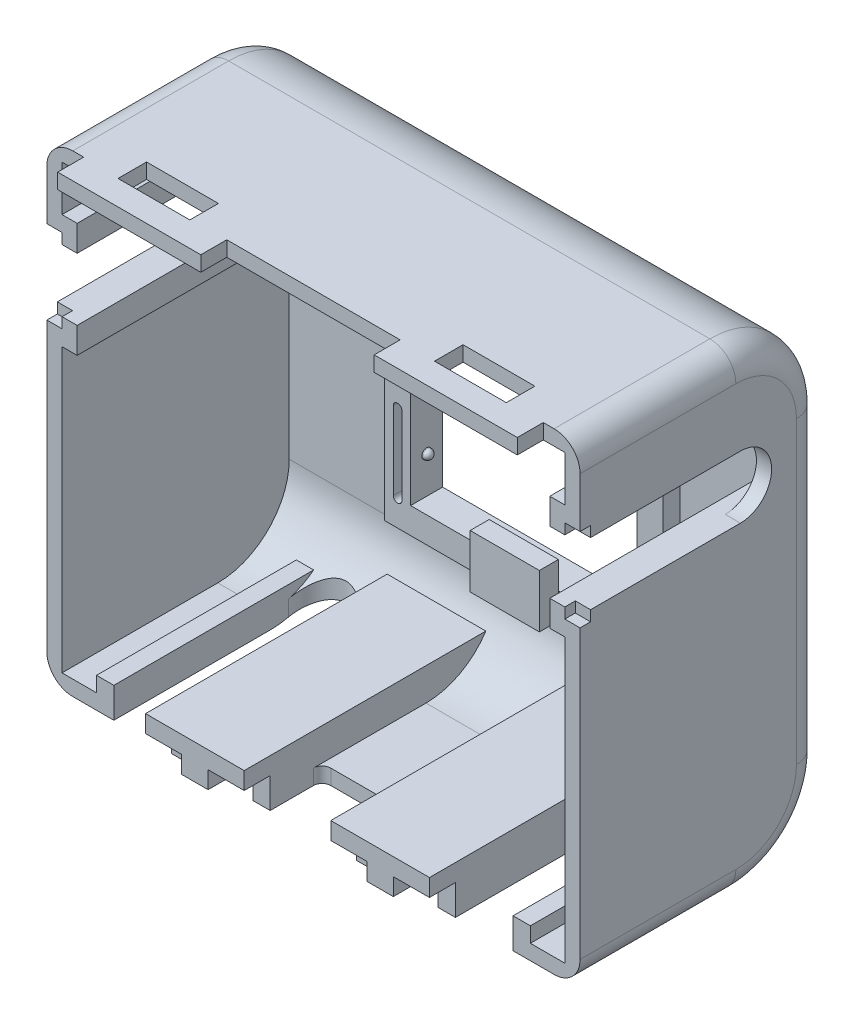
SolidWorks part; units mm, degrees
ref_plane "正面" through (0, 0, 0) normal (0, 0, 1) x (1, 0, 0)
ref_plane "平面" through (0, 0, 0) normal (0, 1, 0) x (1, 0, 0)
ref_plane "右側面" through (0, 0, 0) normal (1, 0, 0) x (0, 0, -1)
sketch "ｽｹｯﾁ1" plane through (0, 0, 0) normal (0, 0, 1) x (1, 0, 0)
  line L0 (0, 0) -> (54, 0) construction
  line L1 (0, 20) -> (54, 20) construction
  line L2 (-1.5, 45.5) -> (55.5, 45.5)
  line L3 (54, 0) -> (54, 40) construction
  line L4 (54, 40) -> (0, 40) construction
  line L5 (0, 40) -> (0, 0) construction
  line L6 (55.5, 45.5) -> (55.5, -5.5)
  line L7 (55.5, -5.5) -> (-1.5, -5.5)
  line L8 (-1.5, -5.5) -> (-1.5, 45.5)
  line L9 (27, 45.5) -> (27, -5.5) construction
  circle A0 centre (2, 2) radius 1.1 construction
  circle A1 centre (52, 2) radius 1.1 construction
  circle A2 centre (52, 38) radius 1.1 construction
  circle A3 centre (2, 38) radius 1.1 construction
  circle A4 centre (2, 38) radius 0.9
  circle A5 centre (2, 38) radius 1.8491
  circle A6 centre (2, 2) radius 1.8491
  circle A7 centre (52, 2) radius 1.8491
  circle A8 centre (52, 38) radius 1.8491
  circle A9 centre (52, 38) radius 0.9
  circle A10 centre (52, 2) radius 0.9
  circle A11 centre (2, 2) radius 0.9
  circle A12 centre (11.0176, 28.1) radius 7
  circle A13 centre (42.9824, 28.1) radius 7
  circle A14 centre (16.5, 8.4) radius 7
  circle A15 centre (37.5, 8.4) radius 7
  dimension "D3" = 2.2
  dimension "D8" = 1.8
  dimension "D9" = 14
  dimension "D10" = 14
  dimension "D11" = 14
  dimension "D12" = 14
  dimension "D1" = 40
  dimension "D2" = 54
  dimension "D4" = 25.5
  dimension "D5" = 25.5
  dimension "D6" = 1.5
  dimension "D7" = 1.5
sketch "ｽｹｯﾁ2" plane through (0, 0, 0) normal (1, 0, 0) x (0, 0, -1)
  line L2 (0, 0) -> (18, 0)
  line L3 (0, 0) -> (0, 54.6)
  line L4 (0, 54.6) -> (18, 54.6)
  line L5 (28, 10) -> (28, 44.6)
  arc A0 (18, 0) -> (28, 10) centre (18, 10) ccw
  arc A1 (18, 54.6) -> (28, 44.6) centre (18, 44.6) cw
  point P8 (28, 54.6)
  dimension "D3" = 10
  dimension "D1" = 28
  dimension "D2" = 54.6
extrude "ﾎﾞｽ - 押し出し1" add sketch "ｽｹｯﾁ2" along normal blind 61.6
shell "ｼｪﾙ1" thickness 1.75 removed face at (30.8, 27.3, 0)
fillet "ﾌｨﾚｯﾄ2" radius 3 10 edges at (0, 54.6, -9) (61.6, 54.6, -9) (0, 0, -9) (0, 2.9289, -25.0711) (0, 27.3, -28) (0, 51.6711, -25.0711) (61.6, 0, -9) (61.6, 2.9289, -25.0711) (61.6, 27.3, -28) (61.6, 51.6711, -25.0711)
sketch "ｽｹｯﾁ3" plane through (0, 0, -26.25) normal (0, 0, -1) x (-1, 0, 0)
  line L0 (-30.8, 44.6) -> (-30.8, 10) construction
  line L1 (-58.6, 44.6) -> (-3, 44.6) construction
  line L2 (-58.6, 10) -> (-3, 10) construction
  line L3 (-30.8, 39.325) -> (-30.8, 15.475) construction
  line L4 (-24.3025, 31.1) -> (-24.3025, 39.225) construction
  line L5 (-34.9975, 31.1) -> (-34.9975, 23.7) construction
  line L6 (-26.6025, 31.1) -> (-26.6025, 23.7) construction
  line L7 (-39.5975, 31.1) -> (-34.9975, 31.1) construction
  line L8 (-39.5975, 31.1) -> (-39.5975, 23.7) construction
  line L9 (-39.5975, 23.7) -> (-34.9975, 23.7) construction
  line L10 (-37.2975, 39.225) -> (-37.2975, 15.575) construction
  line L11 (-22.0025, 23.7) -> (-26.6025, 23.7) construction
  line L12 (-22.0025, 31.1) -> (-22.0025, 23.7) construction
  line L13 (-22.0025, 31.1) -> (-26.6025, 31.1) construction
  line L14 (-30.8, 27.3) -> (-58.6, 27.3) construction
  line L15 (-58.6, 44.6) -> (-58.6, 10) construction
  line L20 (-43.88, 40.48) -> (-43.88, 14.32)
  line L21 (-17.72, 14.32) -> (-17.72, 40.48)
  line L22 (-16.22, 40.48) -> (-16.22, 31.48) construction
  line L23 (-15.72, 40.48) -> (-15.72, 31.48)
  line L24 (-16.72, 40.48) -> (-16.72, 31.48)
  line L25 (-17.72, 40.48) -> (-16.22, 40.48) construction
  line L26 (-17.72, 40.48) -> (-43.88, 40.48)
  line L27 (-16.22, 14.32) -> (-16.22, 23.32) construction
  line L28 (-30.8, 40.8494) -> (-30.8, 13.9506) construction
  line L29 (-45.38, 40.48) -> (-45.38, 31.48) construction
  line L30 (-45.88, 40.48) -> (-45.88, 31.48)
  line L31 (-44.88, 40.48) -> (-44.88, 31.48)
  line L32 (-15.72, 14.32) -> (-15.72, 23.32)
  line L33 (-17.72, 14.32) -> (-43.88, 14.32)
  line L34 (-43.88, 27.4) -> (-17.72, 27.4) construction
  line L35 (-16.72, 14.32) -> (-16.72, 23.32)
  line L36 (-45.38, 14.32) -> (-45.38, 23.32) construction
  line L37 (-45.88, 14.32) -> (-45.88, 23.32)
  line L38 (-44.88, 14.32) -> (-44.88, 23.32)
  arc A0 (-15.72, 40.48) -> (-16.72, 40.48) centre (-16.22, 40.48) ccw
  arc A1 (-16.72, 31.48) -> (-15.72, 31.48) centre (-16.22, 31.48) ccw
  arc A2 (-45.88, 40.48) -> (-44.88, 40.48) centre (-45.38, 40.48) cw
  arc A3 (-44.88, 31.48) -> (-45.88, 31.48) centre (-45.38, 31.48) cw
  arc A4 (-15.72, 14.32) -> (-16.72, 14.32) centre (-16.22, 14.32) cw
  arc A5 (-16.72, 23.32) -> (-15.72, 23.32) centre (-16.22, 23.32) cw
  arc A6 (-45.88, 14.32) -> (-44.88, 14.32) centre (-45.38, 14.32) ccw
  arc A7 (-44.88, 23.32) -> (-45.88, 23.32) centre (-45.38, 23.32) ccw
  point P32 (-16.22, 35.98)
  point P43 (-16.22, 18.82)
  point P53 (-45.38, 35.98)
  point P59 (-45.38, 18.82)
  dimension "D4" = 1
  dimension "D5" = 1
  dimension "D6" = 13.08
extrude "ｶｯﾄ - 押し出し1" cut sketch "ｽｹｯﾁ3" along normal up to vertex (1.75 mm away) up to point (3, 10, -28)
sketch "ｽｹｯﾁ4" [suppressed] plane through (0, 0, -34) normal (0, 0, 1) x (1, 0, 0)
  line L6 (22.0025, 31.1) -> (26.6025, 31.1) construction
  line L7 (22.0025, 23.7) -> (22.0025, 31.1) construction
  line L8 (22.0025, 23.7) -> (26.6025, 23.7) construction
  line L9 (26.6025, 31.1) -> (26.6025, 23.7) construction
  line L10 (39.5975, 23.7) -> (34.9975, 23.7) construction
  line L11 (34.9975, 31.1) -> (34.9975, 23.7) construction
  line L12 (17.9225, 15.575) -> (30.6725, 15.575)
  line L13 (30.6725, 15.575) -> (43.6775, 15.575)
  line L14 (43.6775, 15.575) -> (43.6775, 39.225)
  line L15 (43.6775, 39.225) -> (30.6725, 39.225)
  line L16 (30.6725, 39.225) -> (17.9225, 39.225)
  line L17 (17.9225, 39.225) -> (17.9225, 15.575)
  line L18 (39.5975, 31.1) -> (34.9975, 31.1) construction
  line L19 (39.5975, 31.1) -> (39.5975, 23.7) construction
  line L20 (22.0025, 31.1) -> (26.6025, 31.1)
  line L21 (22.0025, 23.7) -> (22.0025, 31.1)
  line L22 (22.0025, 23.7) -> (26.6025, 23.7)
  line L23 (26.6025, 31.1) -> (26.6025, 23.7)
  line L24 (39.5975, 23.7) -> (34.9975, 23.7)
  line L25 (34.9975, 31.1) -> (34.9975, 23.7)
  line L26 (39.5975, 31.1) -> (34.9975, 31.1)
  line L27 (39.5975, 31.1) -> (39.5975, 23.7)
extrude "ﾎﾞｽ - 押し出し2" [suppressed] add sketch "ｽｹｯﾁ4" along normal blind 3.7
sketch "ｽｹｯﾁ5" [suppressed] plane through (0, 0, -30.3) normal (0, 0, 1) x (1, 0, 0)
  line L9 (20.8725, 31.35) -> (20.8725, 23.45)
  line L10 (17.9225, 31.35) -> (17.9225, 23.45)
  line L11 (43.6775, 31.35) -> (43.6775, 23.45)
  line L12 (40.7275, 23.45) -> (40.7275, 31.35)
  line L13 (43.6775, 37.225) -> (43.6775, 39.225)
  line L14 (43.6775, 39.225) -> (17.9225, 39.225)
  line L15 (17.9225, 37.225) -> (43.6775, 37.225)
  line L16 (43.6775, 17.575) -> (17.9225, 17.575)
  line L17 (17.9225, 15.575) -> (43.6775, 15.575)
  line L18 (17.9225, 31.35) -> (20.8725, 31.35)
  line L19 (17.9225, 23.45) -> (20.8725, 23.45)
  line L20 (40.7275, 31.35) -> (43.6775, 31.35)
  line L21 (40.7275, 23.45) -> (43.6775, 23.45)
  line L22 (17.9225, 39.225) -> (17.9225, 37.225)
  line L23 (17.9225, 17.575) -> (17.9225, 15.575)
  line L24 (43.6775, 17.575) -> (43.6775, 15.575)
extrude "ﾎﾞｽ - 押し出し3" [suppressed] add sketch "ｽｹｯﾁ5" along normal blind 1
ref_plane "平面1" through (-6.5183, 23.4524, -44.2238) normal (0, 1, 0) x (1, 0, 0)
sketch "ｽｹｯﾁ6" plane through (-6.5183, 23.4524, -44.2238) normal (0, 1, 0) x (1, 0, 0)
  line L0 (34.1908, -13.9238) -> (40.4458, -13.9238)
  line L1 (40.4458, -13.9238) -> (40.4458, -21.3238)
  line L2 (40.4458, -21.3238) -> (42.1708, -21.3238)
  line L3 (42.1708, -21.3238) -> (42.1708, -24.3238)
  line L4 (42.1708, -24.3238) -> (32.4658, -24.3238)
  line L5 (32.4658, -24.3238) -> (32.4658, -21.3238)
  line L6 (32.4658, -21.3238) -> (34.1908, -21.3238)
  line L7 (34.1908, -21.3238) -> (34.1908, -13.9238)
extrude "ﾎﾞｽ - 押し出し4" [suppressed] add sketch "ｽｹｯﾁ6" along normal up to vertex
sketch "ｽｹｯﾁ8" plane through (0, 0, 0) normal (-1, 0, 0) x (0, 0, 1)
  line L0 (0, 51.6) -> (0, 3) construction
  line L1 (0, 51.3992) -> (0, 39.6008)
  line L2 (0, 15.1992) -> (0, 3.4008)
  arc A0 (0, 51.3992) -> (0, 39.6008) centre (4.3, 45.5) ccw
  arc A1 (0, 15.1992) -> (0, 3.4008) centre (4.3, 9.3) ccw
sketch "ｽｹｯﾁ9" plane through (0, 0, 0) normal (0, -1, 0) x (1, 0, 0)
  line L0 (58.6, 0) -> (3, 0) construction
  line L1 (56.2992, 0) -> (44.5008, 0)
  line L2 (17.0992, 0) -> (5.3008, 0)
  arc A0 (44.5008, 0) -> (56.2992, 0) centre (50.4, 4.3) ccw
  arc A1 (5.3008, 0) -> (17.0992, 0) centre (11.2, 4.3) ccw
ref_plane "平面2" through (0, 27.3, 0) normal (0, -1, 0) x (-1, 0, 0)
sketch "ｽｹｯﾁ11" plane through (0, 27.3, 0) normal (0, -1, 0) x (-1, 0, 0)
  line L0 (-59.85, 0) -> (-59.85, 18) construction
  line L1 (-59.85, 1.1766) -> (-59.85, 2.4767)
  line L2 (-59.85, 2.3353) -> (-60.3137, 1.8716) construction
  line L3 (-60.3137, 1.8716) -> (-60.3137, 1.2766) construction
  line L4 (-60.3137, 1.2766) -> (-59.85, 1.2766) construction
  line L5 (-60.4137, 1.913) -> (-59.85, 2.4767)
  line L6 (-60.4137, 1.913) -> (-60.4137, 1.1766)
  line L7 (-60.4137, 1.1766) -> (-59.85, 1.1766)
  line L8 (-59.9207, 2.406) -> (-60.4137, 1.913) construction
  line L9 (-30.8, 28) -> (-30.8, 48.4859) construction
  line L10 (-58.6, 28) -> (-3, 28) construction
  line L11 (-1.2863, 1.8716) -> (-1.2863, 1.2766) construction
  line L12 (-1.75, 2.3353) -> (-1.2863, 1.8716) construction
  line L13 (-1.1863, 1.1766) -> (-1.75, 1.1766)
  line L14 (-1.1863, 1.913) -> (-1.1863, 1.1766)
  line L15 (-1.1863, 1.913) -> (-1.75, 2.4767)
  line L16 (-1.2863, 1.2766) -> (-1.75, 1.2766) construction
  line L17 (-1.75, 1.1766) -> (-1.75, 2.4767)
  dimension "D1" = 0.1
  dimension "D2" = 0
ref_plane "平面3" through (30.8, 0, 0) normal (1, 0, 0) x (0, 0, -1)
sketch "ｽｹｯﾁ12" plane through (30.8, 0, 0) normal (1, 0, 0) x (0, 0, -1)
  line L0 (1.7713, 1.2113) -> (1.3013, 1.2113) construction
  line L1 (2.36, 1.8) -> (1.7713, 1.2113) construction
  line L2 (2.4514, 1.75) -> (1.2013, 1.75)
  line L3 (2.36, 52.8) -> (1.7713, 53.3887) construction
  line L4 (1.7713, 53.3887) -> (1.3013, 53.3887) construction
  line L5 (1.3013, 53.3887) -> (1.3013, 52.85) construction
  line L6 (1.8128, 53.4887) -> (2.4514, 52.85)
  line L7 (1.8128, 53.4887) -> (1.2013, 53.4887)
  line L8 (1.2013, 53.4887) -> (1.2013, 52.85)
  line L9 (2.4307, 52.8707) -> (1.8128, 53.4887) construction
  line L10 (18, 52.85) -> (0, 52.85) construction
  line L11 (2.4514, 52.85) -> (1.2013, 52.85)
  line L12 (28, 27.3) -> (38.8234, 27.3) construction
  line L13 (28, 44.6) -> (28, 10) construction
  line L14 (1.2013, 1.1113) -> (1.2013, 1.75)
  line L15 (1.8128, 1.1113) -> (1.2013, 1.1113)
  line L16 (1.8128, 1.1113) -> (2.4514, 1.75)
  dimension "D2" = 0
  dimension "D1" = 0.1
sketch "ｽｹｯﾁ13" plane through (0, 0, 0) normal (0, -1, 0) x (1, 0, 0)
  line L0 (30.8, 0) -> (30.8, -18.5) construction
  line L1 (25.3, -18.5) -> (20.3, -18.5) construction
  line L2 (25.3, -13.5) -> (20.3, -13.5) construction
  line L5 (30.8, -28) -> (30.8, -54.1589) construction
  line L6 (58.6, -28) -> (3, -28) construction
  line L7 (30.8, -13.75) -> (30.8, 13.75) construction
  line L16 (25.3, 0) -> (36.3, 0)
  line L17 (25.3, 0) -> (25.3, -8.5)
  line L18 (25.3, -18.5) -> (36.3, -18.5)
  line L19 (36.3, 0) -> (36.3, -8.5)
  arc A0 (20.3, -13.5) -> (25.3, -18.5) centre (20.3, -18.5) ccw
  arc A1 (25.3, -8.5) -> (20.3, -13.5) centre (20.3, -8.5) cw
  arc A2 (41.3, -13.5) -> (36.3, -18.5) centre (41.3, -18.5) cw
  arc A3 (36.3, -8.5) -> (41.3, -13.5) centre (41.3, -8.5) ccw
  dimension "D3" = 5
  dimension "D5" = 18.5
  dimension "D4" = 5
  dimension "D1" = 5.5
sketch "ｽｹｯﾁ18" plane through (0, 0, -26.25) normal (0, 0, 1) x (1, 0, 0)
  line L0 (43.78, 34.2875) -> (50.5865, 34.2875) construction
  line L2 (43.78, 36.2875) -> (51.48, 36.2875)
  line L3 (43.78, 27.4) -> (57.3963, 27.4) construction
  line L4 (43.78, 32.2875) -> (51.48, 32.2875)
  line L5 (51.48, 22.5125) -> (51.48, 22.6725)
  line L6 (43.78, 36.4475) -> (51.48, 36.4475)
  line L7 (43.62, 36.4475) -> (51.64, 36.4475) construction
  line L8 (43.78, 32.1275) -> (51.48, 32.1275)
  line L9 (43.78, 36.2875) -> (43.78, 32.2875) construction
  line L10 (43.78, 36.2875) -> (43.78, 36.4475)
  line L11 (43.78, 32.2875) -> (43.78, 32.1275)
  line L12 (51.48, 36.2875) -> (51.48, 36.4475)
  line L13 (51.48, 32.2875) -> (51.48, 32.1275)
  line L14 (51.48, 18.5125) -> (51.48, 18.3525)
  line L15 (43.62, 32.1275) -> (51.64, 32.1275) construction
  line L16 (51.64, 36.4475) -> (51.64, 32.1275) construction
  line L17 (51.48, 36.2875) -> (51.48, 32.2875) construction
  line L18 (43.62, 36.4475) -> (43.62, 32.1275) construction
  line L19 (43.78, 22.5125) -> (43.78, 22.6725)
  line L20 (43.78, 18.5125) -> (43.78, 18.3525)
  line L21 (43.78, 22.6725) -> (51.48, 22.6725)
  line L22 (43.78, 18.3525) -> (51.48, 18.3525)
  line L23 (43.78, 22.5125) -> (51.48, 22.5125)
  line L24 (43.78, 18.5125) -> (51.48, 18.5125)
  line L25 (30.8, 15.475) -> (30.8, 5.7005) construction
  line L27 (17.82, 27.4) -> (4.2037, 27.4) construction
  line L28 (17.82, 34.2875) -> (11.0135, 34.2875) construction
  line L29 (17.82, 18.5125) -> (10.12, 18.5125)
  line L30 (17.82, 22.5125) -> (10.12, 22.5125)
  line L31 (17.82, 18.3525) -> (10.12, 18.3525)
  line L32 (17.82, 22.6725) -> (10.12, 22.6725)
  line L33 (17.82, 18.5125) -> (17.82, 18.3525)
  line L34 (17.82, 22.5125) -> (17.82, 22.6725)
  line L35 (10.12, 18.5125) -> (10.12, 18.3525)
  line L36 (10.12, 32.2875) -> (10.12, 32.1275)
  line L37 (10.12, 36.2875) -> (10.12, 36.4475)
  line L38 (17.82, 32.2875) -> (17.82, 32.1275)
  line L39 (17.82, 36.2875) -> (17.82, 36.4475)
  line L40 (17.82, 32.1275) -> (10.12, 32.1275)
  line L41 (17.82, 36.4475) -> (10.12, 36.4475)
  line L42 (10.12, 22.5125) -> (10.12, 22.6725)
  line L43 (17.82, 32.2875) -> (10.12, 32.2875)
  line L44 (17.82, 36.2875) -> (10.12, 36.2875)
  dimension "D1" = 2
  dimension "D2" = 2
  dimension "D4" = 7.7
  dimension "D3" = 0.16
extrude "ｶｯﾄ - 押し出し9" [suppressed] cut sketch "ｽｹｯﾁ18" against normal up to vertex up to point (3, 10, -28)
sketch "ｽｹｯﾁ22" [suppressed] plane through (0, 0, -34) normal (0, 0, -1) x (-1, 0, 0)
  line L0 (-43.78, 36.2875) -> (-43.78, 32.2875) construction
  line L1 (-43.78, 36.2875) -> (-51.48, 36.2875) construction
  line L2 (-51.48, 32.2875) -> (-43.78, 32.2875) construction
  line L3 (-43.78, 36.2875) -> (-43.78, 32.2875) construction
  line L4 (-43.78, 36.2875) -> (-47.78, 36.2875) construction
  line L5 (-47.78, 32.2875) -> (-43.78, 32.2875) construction
  line L6 (-47.78, 36.2875) -> (-47.78, 32.2875) construction
  line L7 (-43.78, 27.4) -> (-69.4613, 27.4) construction
  line L8 (-43.78, 32.1275) -> (-43.78, 22.6725) construction
  line L9 (-13.2, 27.4) -> (13.2, 27.4) construction
  line L10 (-45.78, 36.2875) -> (-45.78, 32.2875)
  line L11 (-45.78, 18.5125) -> (-45.78, 22.5125)
  arc A0 (-45.78, 36.2875) -> (-45.78, 32.2875) centre (-45.78, 34.2875) ccw
  arc A1 (-45.78, 18.5125) -> (-45.78, 22.5125) centre (-45.78, 20.5125) cw
  dimension "D1" = 4
sketch "ｽｹｯﾁ23" [suppressed] plane through (0, 0, -34) normal (0, 0, -1) x (-1, 0, 0)
  line L0 (-30.8, 39.325) -> (-30.8, 46.4281) construction
  line L1 (-17.82, 39.325) -> (-43.78, 39.325) construction
  line L2 (-30.8, 17.05) -> (-30.8, -17.05) construction
  line L3 (-15.82, 32.2875) -> (-15.82, 36.2875)
  line L4 (-45.78, 18.5125) -> (-45.78, 22.5125)
  line L5 (-45.78, 18.5125) -> (-45.78, 22.5125) construction
  line L6 (-45.78, 32.2875) -> (-45.78, 36.2875)
  line L7 (-45.78, 32.2875) -> (-45.78, 36.2875) construction
  line L8 (-15.82, 18.5125) -> (-15.82, 22.5125)
  arc A0 (-15.82, 36.2875) -> (-15.82, 32.2875) centre (-15.82, 34.2875) cw
  arc A1 (-45.78, 22.5125) -> (-45.78, 18.5125) centre (-45.78, 20.5125) ccw
  arc A2 (-45.78, 22.5125) -> (-45.78, 18.5125) centre (-45.78, 20.5125) ccw construction
  arc A3 (-45.78, 36.2875) -> (-45.78, 32.2875) centre (-45.78, 34.2875) ccw
  arc A4 (-45.78, 36.2875) -> (-45.78, 32.2875) centre (-45.78, 34.2875) ccw construction
  arc A5 (-15.82, 22.5125) -> (-15.82, 18.5125) centre (-15.82, 20.5125) cw
  dimension "D1" = 0
  dimension "D2" = 0
sketch "ｽｹｯﾁ24" [suppressed] plane through (0, 0, -26) normal (0, 0, 1) x (1, 0, 0)
  line L0 (15.72, 31.48) -> (15.72, 40.48) construction
  line L1 (16.72, 40.48) -> (16.72, 31.48) construction
  line L2 (15.72, 14.32) -> (15.72, 23.32) construction
  line L3 (16.72, 23.32) -> (16.72, 14.32) construction
  line L4 (17.72, 14.32) -> (17.72, 40.48) construction
  line L5 (43.88, 14.32) -> (17.72, 14.32) construction
  line L6 (43.88, 40.48) -> (43.88, 14.32) construction
  line L7 (17.72, 40.48) -> (43.88, 40.48) construction
  line L8 (45.88, 40.48) -> (45.88, 31.48) construction
  line L9 (44.88, 31.48) -> (44.88, 40.48) construction
  line L10 (45.88, 23.32) -> (45.88, 14.32) construction
  line L11 (44.88, 14.32) -> (44.88, 23.32) construction
  line L12 (15.72, 31.48) -> (15.72, 40.48)
  line L13 (16.72, 40.48) -> (16.72, 31.48)
  line L14 (15.72, 14.32) -> (15.72, 23.32)
  line L15 (16.72, 23.32) -> (16.72, 14.32)
  line L16 (17.72, 14.32) -> (17.72, 40.48)
  line L17 (43.88, 14.32) -> (17.72, 14.32)
  line L18 (43.88, 40.48) -> (43.88, 14.32)
  line L19 (17.72, 40.48) -> (43.88, 40.48)
  line L20 (45.88, 40.48) -> (45.88, 31.48)
  line L21 (44.88, 31.48) -> (44.88, 40.48)
  line L22 (45.88, 23.32) -> (45.88, 14.32)
  line L23 (44.88, 14.32) -> (44.88, 23.32)
  line L24 (14.72, 43.48) -> (46.88, 43.48)
  line L25 (46.88, 43.48) -> (46.88, 11.32)
  line L26 (46.88, 11.32) -> (14.72, 11.32)
  line L27 (14.72, 11.32) -> (14.72, 43.48)
  arc A0 (16.72, 40.48) -> (15.72, 40.48) centre (16.22, 40.48) ccw construction
  arc A1 (16.72, 23.32) -> (15.72, 23.32) centre (16.22, 23.32) ccw construction
  arc A2 (15.72, 14.32) -> (16.72, 14.32) centre (16.22, 14.32) ccw construction
  arc A3 (45.88, 40.48) -> (44.88, 40.48) centre (45.38, 40.48) ccw construction
  arc A4 (45.88, 23.32) -> (44.88, 23.32) centre (45.38, 23.32) ccw construction
  arc A5 (44.88, 14.32) -> (45.88, 14.32) centre (45.38, 14.32) ccw construction
  arc A6 (16.72, 40.48) -> (15.72, 40.48) centre (16.22, 40.48) ccw
  arc A7 (16.72, 23.32) -> (15.72, 23.32) centre (16.22, 23.32) ccw
  arc A8 (15.72, 14.32) -> (16.72, 14.32) centre (16.22, 14.32) ccw
  arc A9 (45.88, 40.48) -> (44.88, 40.48) centre (45.38, 40.48) ccw
  arc A10 (45.88, 23.32) -> (44.88, 23.32) centre (45.38, 23.32) ccw
  arc A11 (44.88, 14.32) -> (45.88, 14.32) centre (45.38, 14.32) ccw
  arc A12 (15.72, 31.48) -> (16.72, 31.48) centre (16.22, 31.48) ccw construction
  arc A13 (44.88, 31.48) -> (45.88, 31.48) centre (45.38, 31.48) ccw construction
  arc A14 (15.72, 31.48) -> (16.72, 31.48) centre (16.22, 31.48) ccw
  arc A15 (44.88, 31.48) -> (45.88, 31.48) centre (45.38, 31.48) ccw
  dimension "D1" = 3
extrude "ﾎﾞｽ - 押し出し9" [suppressed] add sketch "ｽｹｯﾁ24" along normal blind 1.7
sketch "ｽｹｯﾁ25" plane through (0, 0, 0) normal (0, -1, 0) x (1, 0, 0)
  line L3 (30.8, -35.4132) -> (30.8, 29.1901) construction
  line L4 (30.8, -28) -> (30.8, -48.4859) construction
  line L5 (30.8, -13.75) -> (30.8, 13.75) construction
  line L6 (25.3, 0) -> (36.3, 0) construction
  line L7 (25.8, 0) -> (35.8, 0)
  line L8 (25.8, 0) -> (25.8, -6)
  line L9 (25.8, -6) -> (35.8, -6)
  line L12 (35.8, 0) -> (35.8, -6)
  dimension "D2" = 5
  dimension "D1" = 5
  dimension "D3" = 6
extrude "ｶｯﾄ - 押し出し10" cut sketch "ｽｹｯﾁ25" against normal blind 1.75
sketch "ｽｹｯﾁ26" plane through (61.6, 0, 0) normal (1, 0, 0) x (0, 0, -1)
  line L0 (0, 37.3902) -> (18.5241, 37.3902)
  line L1 (0, 51.6) -> (0, 3) construction
  line L2 (18.5241, 44.6) -> (0, 44.6)
  line L4 (18.5241, 37.3902) -> (18.5241, 44.6) construction
  line L5 (0, 37.3902) -> (0, 44.6)
  arc A0 (18.5241, 37.3902) -> (18.5241, 44.6) centre (18.5241, 40.9951) ccw
extrude "ｶｯﾄ - 押し出し11" cut sketch "ｽｹｯﾁ26" against normal up to vertex (61.6 mm away) up to point (0, 44.6, -25)
sketch "ｽｹｯﾁ27" plane through (0, 0, 0) normal (0, -1, 0) x (1, 0, 0)
  line L0 (7.7395, 0) -> (7.7395, -20.1658)
  line L1 (25.8, 0) -> (3, 0) construction
  line L2 (14.4, 0) -> (14.4, -20.1658)
  line L3 (14.4, -20.1658) -> (7.7395, -20.1658) construction
  line L4 (7.7395, 0) -> (14.4, 0)
  line L5 (30.8, -28) -> (30.8, -51.2795) construction
  line L6 (58.6, -28) -> (3, -28) construction
  line L7 (47.2, -20.1658) -> (53.8605, -20.1658) construction
  line L8 (53.8605, 0) -> (47.2, 0)
  line L9 (47.2, 0) -> (47.2, -20.1658)
  line L10 (53.8605, 0) -> (53.8605, -20.1658)
  arc A0 (7.7395, -20.1658) -> (14.4, -20.1658) centre (11.0698, -20.1658) ccw
  arc A1 (53.8605, -20.1658) -> (47.2, -20.1658) centre (50.5302, -20.1658) cw
extrude "ｶｯﾄ - 押し出し12" cut sketch "ｽｹｯﾁ27" against normal up to next
sketch "ｽｹｯﾁ28" plane through (0, 0, 0) normal (0, 0, 1) x (1, 0, 0)
  line L0 (1.75, 40.9951) -> (-4.5642, 40.9951) construction
  line L1 (1.75, 44.6) -> (3.5, 44.6)
  line L2 (1.75, 44.6) -> (1.75, 46.6)
  line L3 (1.75, 46.6) -> (3.5, 46.6)
  line L4 (3.5, 44.6) -> (3.5, 46.6)
  line L5 (1.75, 37.3902) -> (1.75, 44.6) construction
  line L6 (3.5, 37.3902) -> (3.5, 35.3902)
  line L7 (1.75, 35.3902) -> (3.5, 35.3902)
  line L8 (1.75, 37.3902) -> (1.75, 35.3902)
  line L9 (1.75, 37.3902) -> (3.5, 37.3902)
  line L10 (30.8, 54.6) -> (30.8, 62.0543) construction
  line L11 (7.7395, 1.75) -> (5.7395, 1.75)
  line L12 (7.7395, 1.75) -> (7.7395, 3.5)
  line L13 (7.7395, 3.5) -> (5.7395, 3.5)
  line L14 (5.7395, 1.75) -> (5.7395, 3.5)
  line L15 (14.4, 1.75) -> (16.4, 1.75)
  line L16 (14.4, 1.75) -> (14.4, 3.5)
  line L17 (14.4, 3.5) -> (16.4, 3.5)
  line L18 (16.4, 1.75) -> (16.4, 3.5)
  line L19 (58.6, 54.6) -> (3, 54.6) construction
  line L20 (30.8, -13.75) -> (30.8, 13.75) construction
  line L21 (59.85, 40.9951) -> (66.1642, 40.9951) construction
  line L22 (45.2, 1.75) -> (45.2, 3.5)
  line L23 (47.2, 3.5) -> (45.2, 3.5)
  line L24 (47.2, 1.75) -> (47.2, 3.5)
  line L25 (47.2, 1.75) -> (45.2, 1.75)
  line L26 (55.8605, 1.75) -> (55.8605, 3.5)
  line L27 (53.8605, 3.5) -> (55.8605, 3.5)
  line L28 (53.8605, 1.75) -> (53.8605, 3.5)
  line L29 (53.8605, 1.75) -> (55.8605, 1.75)
  line L30 (59.85, 37.3902) -> (58.1, 37.3902)
  line L31 (59.85, 37.3902) -> (59.85, 35.3902)
  line L32 (59.85, 35.3902) -> (58.1, 35.3902)
  line L33 (58.1, 37.3902) -> (58.1, 35.3902)
  line L34 (58.1, 44.6) -> (58.1, 46.6)
  line L35 (59.85, 46.6) -> (58.1, 46.6)
  line L36 (59.85, 44.6) -> (59.85, 46.6)
  line L37 (59.85, 44.6) -> (58.1, 44.6)
  line L38 (20.1, 1.75) -> (20.1, -7.0091) construction
  line L39 (25.8, 1.75) -> (14.4, 1.75) construction
  line L40 (23.8, 1.75) -> (23.8, 3.5)
  line L41 (25.8, 3.5) -> (23.8, 3.5)
  line L42 (25.8, 1.75) -> (25.8, 3.5)
  line L43 (25.8, 1.75) -> (23.8, 1.75)
  line L44 (35.8, 1.75) -> (37.8, 1.75)
  line L45 (35.8, 1.75) -> (35.8, 3.5)
  line L46 (35.8, 3.5) -> (37.8, 3.5)
  line L47 (37.8, 1.75) -> (37.8, 3.5)
  dimension "D1" = 1.75
  dimension "D2" = 2
  dimension "D3" = 1.75
  dimension "D4" = 2
  dimension "D5" = 2
  dimension "D6" = 1.75
extrude "ﾎﾞｽ - 押し出し10" add sketch "ｽｹｯﾁ28" against normal up to next
sketch "ｽｹｯﾁ31" plane through (0, 54.6, 0) normal (0, 1, 0) x (1, 0, 0)
  line L0 (4.25, 0) -> (4.25, -3)
  line L1 (58.6, 0) -> (3, 0) construction
  line L2 (20.7851, 0) -> (20.7851, -3)
  line L3 (4.25, 0) -> (20.7851, 0)
  line L4 (4.25, -3) -> (20.7851, -3)
  line L5 (30.8, 28) -> (30.8, 54.5632) construction
  line L6 (58.6, 28) -> (3, 28) construction
  line L7 (40.0649, 0) -> (40.0649, -3) construction
  line L8 (3.5, 0) -> (3.5, -3) construction
  line L9 (21.5351, 0) -> (21.5351, -3) construction
  line L12 (58.1, 0) -> (58.1, -3) construction
  line L13 (57.35, -3) -> (40.8149, -3)
  line L14 (57.35, 0) -> (40.8149, 0)
  line L15 (40.8149, 0) -> (40.8149, -3)
  line L16 (57.35, 0) -> (57.35, -3)
  dimension "D1" = 0.75
  dimension "D2" = 0.75
extrude "ﾎﾞｽ - 押し出し11" add sketch "ｽｹｯﾁ31" against normal up to vertex (1.75 mm away) separate body up to point (59.85, 52.85, 0)
combine bodies "組み合わせ1" operation type add bodies to combine 131 132 133
sketch "ｽｹｯﾁ32" plane through (0, 54.6, 0) normal (0, 1, 0) x (1, 0, 0)
  line L8 (53.08, 0) -> (45.08, 0) construction
  line L9 (53.08, 0) -> (53.08, 3) construction
  line L10 (53.08, 3) -> (45.08, 3) construction
  line L11 (45.08, 3) -> (45.08, 0) construction
  line L12 (16.52, 0) -> (16.52, 3) construction
  line L13 (16.52, 0) -> (8.52, 0) construction
  line L14 (16.52, 3) -> (8.52, 3) construction
  line L15 (8.52, 3) -> (8.52, 0) construction
  line L16 (53.23, -0.15) -> (44.93, -0.15)
  line L17 (44.93, 3.15) -> (44.93, -0.15)
  line L18 (53.23, 3.15) -> (44.93, 3.15)
  line L19 (53.23, -0.15) -> (53.23, 3.15)
  line L20 (16.67, -0.15) -> (16.67, 3.15)
  line L21 (16.67, 3.15) -> (8.37, 3.15)
  line L22 (8.37, 3.15) -> (8.37, -0.15)
  line L23 (16.67, -0.15) -> (8.37, -0.15)
  dimension "D1" = 0.15
extrude "ｶｯﾄ - 押し出し14" cut sketch "ｽｹｯﾁ32" against normal up to next
sketch "ｽｹｯﾁ33" plane through (0, 0, 0) normal (0, 0, 1) x (1, 0, 0)
  line L0 (15.3, 0) -> (25.3, 0) construction
  line L1 (16.4, 1.75) -> (16.4, 3.5)
  line L2 (16.4, 1.75) -> (16.4, 0)
  line L3 (16.4, 0) -> (23.8, 0)
  line L4 (23.8, 1.75) -> (23.8, 0)
  line L5 (36.3, 0) -> (46.3, 0) construction
  line L6 (16.4, 1.75) -> (16.4, 3.5) construction
  line L7 (45.2, 1.75) -> (45.2, 0)
  line L8 (45.2, 0) -> (37.8, 0)
  line L9 (37.8, 1.75) -> (37.8, 0)
  line L10 (16.4, 1.75) -> (16.4, 3.5) construction
  line L11 (16.4, 3.5) -> (23.8, 3.5)
  line L12 (23.8, 3.5) -> (23.8, 1.75) construction
  line L13 (25.8, 3.5) -> (23.8, 3.5) construction
  line L14 (23.8, 3.5) -> (23.8, 1.75)
  line L15 (37.8, 1.75) -> (37.8, 3.5)
  line L16 (37.8, 3.5) -> (35.8, 3.5) construction
  line L17 (35.8, 3.5) -> (37.8, 3.5) construction
  line L18 (37.8, 3.5) -> (45.2, 3.5)
  line L19 (45.2, 3.5) -> (47.2, 3.5) construction
  line L20 (45.2, 3.5) -> (45.2, 1.75)
extrude "ｶｯﾄ - 押し出し15" cut sketch "ｽｹｯﾁ33" against normal through all
sketch "ｽｹｯﾁ34" plane through (0, 0, 0) normal (0, 0, 1) x (1, 0, 0)
  line L1 (14.4, 3.5) -> (25.8, 3.5)
  line L2 (14.4, 3.5) -> (14.4, 5.5)
  line L3 (14.4, 5.5) -> (25.8, 5.5)
  line L4 (25.8, 3.5) -> (25.8, 5.5)
  line L5 (35.8, 3.5) -> (47.2, 3.5)
  line L6 (35.8, 3.5) -> (35.8, 5.5)
  line L7 (35.8, 5.5) -> (47.2, 5.5)
  line L8 (47.2, 3.5) -> (47.2, 5.5)
  dimension "D1" = 2
  dimension "D2" = 2
extrude "ﾎﾞｽ - 押し出し12" add sketch "ｽｹｯﾁ34" against normal up to next
sketch "ｽｹｯﾁ36" plane through (0, 0, 0) normal (0, 0, 1) x (1, 0, 0)
  line L0 (47.2, 5.5) -> (47.2, 0) construction
  line L1 (35.8, 5.5) -> (47.2, 5.5)
  line L2 (35.8, 5.5) -> (35.8, 3.5)
  line L3 (35.8, 3.5) -> (47.2, 3.5)
  line L4 (47.2, 5.5) -> (47.2, 3.5)
  line L5 (25.8, 5.5) -> (25.8, 0) construction
  line L6 (14.4, 5.5) -> (25.8, 5.5)
  line L7 (14.4, 5.5) -> (14.4, 3.5)
  line L8 (14.4, 3.5) -> (25.8, 3.5)
  line L9 (25.8, 5.5) -> (25.8, 3.5)
extrude "ﾎﾞｽ - 押し出し14" add sketch "ｽｹｯﾁ36" along normal up to vertex (3 mm away) up to point (4.25, 52.85, 3)
sketch "ｽｹｯﾁ37" plane through (0, 3.5, 0) normal (0, -1, 0) x (1, 0, 0)
  line L0 (41.5, 3) -> (41.5, -5.5779) construction
  line L1 (35.8, 3) -> (47.2, 3) construction
  line L3 (39.975, 3) -> (43.025, 3)
  line L4 (39.975, 3) -> (39.975, 0.6)
  line L5 (39.975, 0.6) -> (43.025, 0.6)
  line L6 (43.025, 3) -> (43.025, 0.6)
  dimension "D1" = 1.525
  dimension "D2" = 1.525
  dimension "D3" = 2.4
extrude "ﾎﾞｽ - 押し出し15" add sketch "ｽｹｯﾁ37" along normal blind 2
mirror "ﾐﾗｰ1" about plane through (30.8, 0, 0) normal (1, 0, 0) of "ﾎﾞｽ - 押し出し15"
fillet "ﾌｨﾚｯﾄ3" radius 1 2 edges at (35.8, 0.875, -6) (25.8, 0.875, -6)
sketch "ｽｹｯﾁ38" plane through (0, 0, -26.25) normal (0, 0, 1) x (1, 0, 0)
  line L0 (46.88, 43.48) -> (14.72, 43.48)
  line L1 (14.72, 43.48) -> (14.72, 11.32)
  line L2 (45.88, 31.48) -> (45.88, 40.48)
  line L3 (44.88, 40.48) -> (44.88, 31.48)
  line L4 (50.0929, 47.1848) -> (11.5071, 46.9401) construction
  line L5 (11.5071, 46.9401) -> (11.5071, 7.4488) construction
  line L6 (11.5071, 7.4488) -> (50.0929, 7.6935) construction
  line L7 (50.0929, 7.6935) -> (50.0929, 47.1848) construction
  line L8 (45.88, 14.32) -> (45.88, 23.32)
  line L9 (44.88, 23.32) -> (44.88, 14.32)
  line L10 (15.72, 23.32) -> (15.72, 14.32)
  line L11 (16.72, 14.32) -> (16.72, 23.32)
  line L12 (16.72, 31.48) -> (16.72, 40.48)
  line L13 (15.72, 40.48) -> (15.72, 31.48)
  line L14 (14.72, 11.32) -> (46.88, 11.32)
  line L15 (46.88, 11.32) -> (46.88, 43.48)
  line L16 (17.72, 40.48) -> (17.72, 14.32)
  line L17 (43.88, 40.48) -> (17.72, 40.48)
  line L18 (43.88, 14.32) -> (43.88, 40.48)
  line L19 (17.72, 14.32) -> (43.88, 14.32)
  arc A0 (44.88, 31.48) -> (45.88, 31.48) centre (45.38, 31.48) ccw
  arc A1 (45.88, 40.48) -> (44.88, 40.48) centre (45.38, 40.48) ccw
  arc A2 (45.88, 23.32) -> (44.88, 23.32) centre (45.38, 23.32) ccw
  arc A3 (44.88, 14.32) -> (45.88, 14.32) centre (45.38, 14.32) ccw
  arc A4 (16.72, 23.32) -> (15.72, 23.32) centre (16.22, 23.32) ccw
  arc A5 (15.72, 14.32) -> (16.72, 14.32) centre (16.22, 14.32) ccw
  arc A6 (15.72, 31.48) -> (16.72, 31.48) centre (16.22, 31.48) ccw
  arc A7 (16.72, 40.48) -> (15.72, 40.48) centre (16.22, 40.48) ccw
extrude "ﾎﾞｽ - 押し出し16" add sketch "ｽｹｯﾁ38" along normal blind 1.95
sketch "ｽｹｯﾁ39" plane through (0, 0, -24.3) normal (0, 0, 1) x (1, 0, 0)
  line L0 (30.8, 43.48) -> (30.8, 11.32) construction
  line L1 (46.88, 43.48) -> (14.72, 43.48) construction
  line L2 (14.72, 11.32) -> (46.88, 11.32) construction
  line L3 (46.88, 27.4) -> (14.72, 27.4) construction
  line L4 (26.8, 43.48) -> (34.8, 43.48)
  line L5 (26.8, 43.48) -> (26.8, 37.33)
  line L6 (26.8, 37.33) -> (34.8, 37.33)
  line L7 (34.8, 43.48) -> (34.8, 37.33)
  line L8 (46.88, 11.32) -> (46.88, 43.48) construction
  line L9 (14.72, 43.48) -> (14.72, 11.32) construction
  line L10 (34.8, 11.32) -> (34.8, 17.47)
  line L11 (26.8, 17.47) -> (34.8, 17.47)
  line L12 (26.8, 11.32) -> (26.8, 17.47)
  line L13 (26.8, 11.32) -> (34.8, 11.32)
  dimension "D1" = 6.15
  dimension "D2" = 4
  dimension "D3" = 4
extrude "ﾎﾞｽ - 押し出し17" add sketch "ｽｹｯﾁ39" along normal blind 2.2
ref_plane "平面4" through (0, 0, -26.15) normal (0, 0, 1) x (1, 0, 0)
sketch "ｽｹｯﾁ40" plane through (0, 0, -26.15) normal (0, 0, 1) x (1, 0, 0)
  line L0 (45.88, 35.98) -> (43.88, 35.98) construction
  line L1 (45.88, 31.48) -> (45.88, 40.48) construction
  line L2 (43.88, 14.32) -> (43.88, 40.48) construction
  line L3 (43.78, 35.98) -> (43.78, 36.53) construction
  line L4 (43.78, 36.53) -> (43.88, 36.53) construction
  line L5 (43.88, 35.98) -> (43.23, 35.98)
  line L6 (43.88, 35.98) -> (43.88, 36.5392)
  arc A0 (43.78, 36.53) -> (43.23, 35.98) centre (43.78, 35.98) ccw
  arc A1 (43.88, 36.5392) -> (43.78, 36.53) centre (43.78, 37.08) cw
  dimension "D1" = 1.1
revolve "回転1" add sketch "ｽｹｯﾁ40" angle 360 about L0
mirror "ﾐﾗｰ2" about plane through (0, 27.3, 0) normal (0, -1, 0) of "回転1"
mirror "ﾐﾗｰ3" about plane through (30.8, 0, 0) normal (1, 0, 0) of "ﾐﾗｰ2", "回転1"
sketch "ｽｹｯﾁ42" plane through (0, 0, 0) normal (-1, 0, 0) x (0, 0, 1)
  line L0 (-18.5241, 44.6) -> (0, 44.6) construction
  line L1 (0, 44.6) -> (-1.2119, 44.6)
  line L2 (0, 44.6) -> (0, 45.814)
  line L3 (0, 45.814) -> (-1.2119, 45.814)
  line L4 (-1.2119, 44.6) -> (-1.2119, 45.814)
  line L5 (-1.0619, 45.664) -> (-1.0619, 43.3705) construction
  line L6 (-1.0619, 45.664) -> (1.0633, 45.664) construction
  line L7 (-22.129, 40.9951) -> (-3.4001, 40.9951) construction
  line L8 (-1.0619, 36.3262) -> (1.0633, 36.3262) construction
  line L9 (-1.0619, 36.3262) -> (-1.0619, 38.6197) construction
  line L10 (-1.2119, 37.3902) -> (-1.2119, 36.1762)
  line L11 (0, 36.1762) -> (-1.2119, 36.1762)
  line L12 (0, 37.3902) -> (0, 36.1762)
  line L13 (0, 37.3902) -> (-1.2119, 37.3902)
  arc A0 (-18.5241, 44.6) -> (-18.5241, 37.3902) centre (-18.5241, 40.9951) ccw construction
  dimension "D1" = 0.15
  dimension "D2" = 0.15
extrude "ｶｯﾄ - 押し出し17" cut sketch "ｽｹｯﾁ42" against normal blind 1.76
sketch "ｽｹｯﾁ43" plane through (0, 0, 0) normal (0, 0, 1) x (1, 0, 0)
  line L0 (3.5, 46.6) -> (1.75, 46.6) construction
  line L1 (3.5, 46.6) -> (1.75, 46.6)
  line L2 (3.5, 46.6) -> (3.5, 47.6)
  line L3 (3.5, 47.6) -> (1.75, 47.6)
  line L4 (1.75, 46.6) -> (1.75, 47.6)
  line L5 (3.5, 44.6) -> (3.5, 46.6) construction
  line L6 (1.75, 52.85) -> (1.75, 46.6) construction
  line L7 (1.75, 35.3902) -> (1.75, 1.75) construction
  line L8 (1.75, 35.3902) -> (3.5, 35.3902)
  line L9 (1.75, 35.3902) -> (1.75, 34.3902)
  line L10 (1.75, 34.3902) -> (3.5, 34.3902)
  line L11 (3.5, 35.3902) -> (3.5, 34.3902)
  dimension "D1" = 1
  dimension "D2" = 1
extrude "ﾎﾞｽ - 押し出し18" add sketch "ｽｹｯﾁ43" against normal up to next
mirror "ﾐﾗｰ4" about plane through (30.8, 0, 0) normal (1, 0, 0) of "ﾎﾞｽ - 押し出し18", "ｶｯﾄ - 押し出し17"
